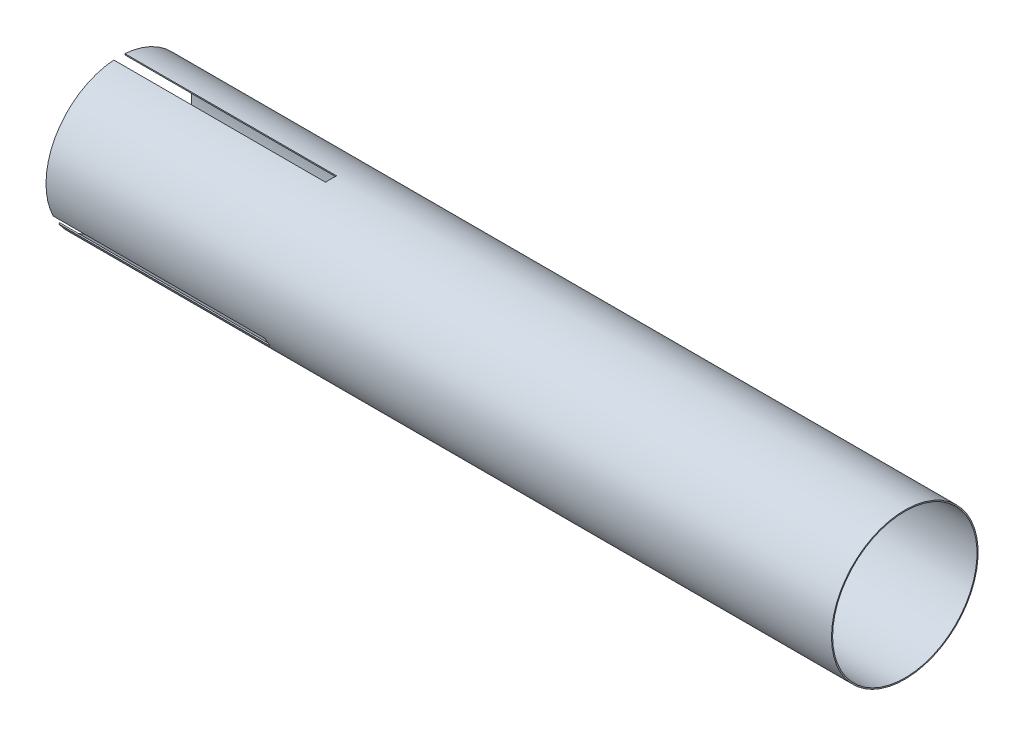
SolidWorks part; units mm, degrees
ref_plane "Plan de face" through (0, 0, 0) normal (0, 0, 1) x (1, 0, 0)
ref_plane "Plan de dessus" through (0, 0, 0) normal (0, 1, 0) x (1, 0, 0)
ref_plane "Plan de droite" through (0, 0, 0) normal (1, 0, 0) x (0, 0, -1)
sketch "Esquisse1" plane through (0, 0, 0) normal (0, 0, 1) x (1, 0, 0)
  line L0 (0, 0) -> (0, 76.182) construction
  line L1 (0, 0) -> (142.5133, 0) construction
  line L2 (0, 76.182) -> (816, 76.182)
  line L3 (0, 76.182) -> (0, -76.182) construction
  line L4 (0, 75) -> (816, 75)
  line L5 (816, 76.182) -> (816, 75)
  line L6 (0, -76.182) -> (816, -76.182) construction
  line L7 (0, 76.182) -> (0, 75)
  dimension "D1" = 152.364
  dimension "D3" = 816
  dimension "D2" = 150
revolve "Révolution1" add sketch "Esquisse1" angle 360 about L1
sketch "Esquisse2" plane through (0, 0, 0) normal (0, 1, 0) x (1, 0, 0)
  line L0 (0, 76.182) -> (0, -76.182) construction
  line L1 (0, -5.741) -> (220, -5.741)
  line L2 (0, -5.741) -> (0, 5.741)
  line L3 (0, 5.741) -> (220, 5.741)
  line L4 (220, -5.741) -> (220, 5.741)
  dimension "D1" = 11.482
  dimension "D2" = 220
extrude "Enlèv. mat.-Extru.1" cut sketch "Esquisse2" along normal through all
pattern_circular "Répétition circulaire1" count 3 over 240 about axis through (816, 0, 0) along (-1, 0, 0) of "Enlèv. mat.-Extru.1"
equation "\"D3@Esquisse1\"=\"l_lower_body_tube\""
equation "\"D2@Esquisse1\"=\"d_i_tube\""
equation "\"D2@Esquisse2\"= \"l_fin_cut\""
equation "\"d_i_tube\"= 150mm'Inner Rocket Body Composite Tube Diameter"
equation "\"t_tube\"= 1.182mm'Thickness of Rocket Body Composite Tube"
equation "\"l_upper_body_tube\"= 949.3mm'Upper Rocket Body Composite Tube length"
equation "\"l_lower_body_tube\"= 816mm'Lower Rocket Body Composite Tube Length"
equation "\"d_a_NC\"= 154mm'Outer Diameter of Nosecone base"
equation "\"d_i_phenolic_tube\"= 152.3mm'Inner Phenolic Tube Diameter"
equation "\"t_phenolic_tube\"= 2mm'Thickness of Phenolic Body Tube"
equation "\"l_fin_cut\"= 220mm'Length of fin on Motor Retainer"
equation "\"t_SW-Panel\"= 11.482mm'Thickness of Sandwich-Panel"
equation "\"l_motor_tube\"=610mm'Length of phenolic motor tube"
equation "\"d_i_motor_tube\"=99.06mm'Inner diameter of phenolic motor tube"
equation "\"t_motor_tube\"=1.58mm'Thicknes of phenolic motor tube"
equation "\"l_cut_fin_centering\"=13mm'Length of cut for fin alignement on fin centering rings"
equation "\"l_M3_threaded_rods\"=220mm'Length of M3 threaded rods for thrust plate force transmission"
